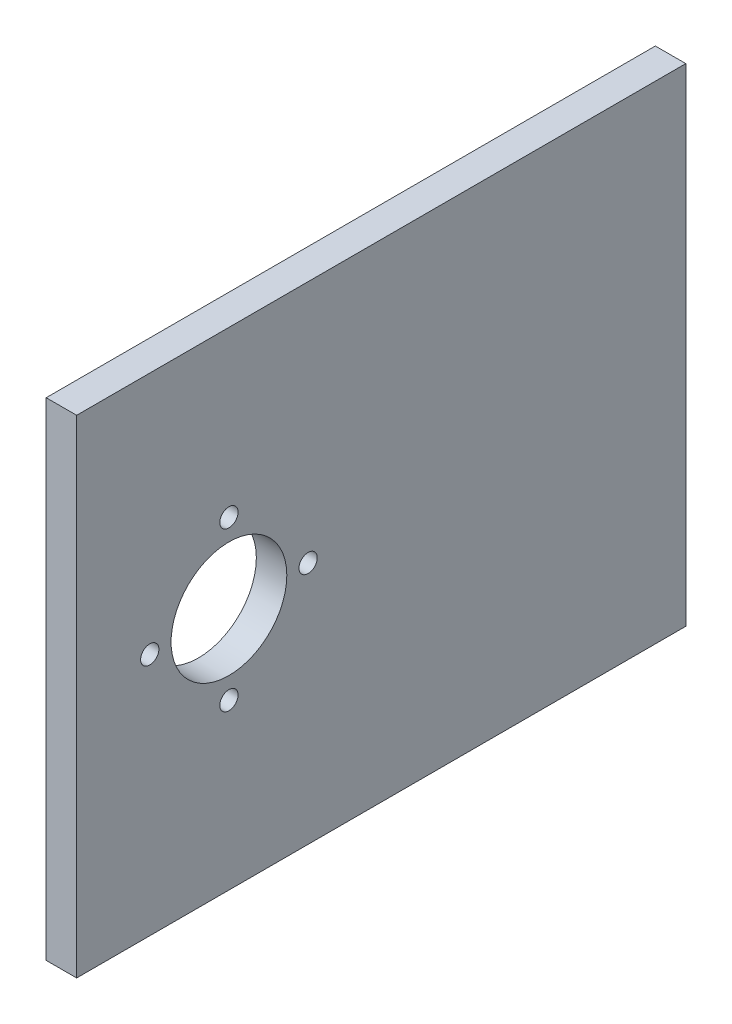
SolidWorks part; units mm, degrees
ref_plane "Front Plane" through (0, 0, 0) normal (1, 0, 0) x (0, 1, 0)
ref_plane "Top Plane" through (0, 0, 0) normal (0, 0, 1) x (0, 1, 0)
ref_plane "Right Plane" through (0, 0, 0) normal (0, 1, 0) x (-1, 0, 0)
sketch "Sketch1" plane through (0, 0, 0) normal (1, 0, 0) x (0, 1, 0)
  line L0 (-40, 25) -> (40, 25) construction
  line L1 (-40, -50) -> (40, -50)
  line L2 (-40, -50) -> (-40, 50)
  line L3 (-40, 50) -> (40, 50)
  line L4 (40, -50) -> (40, 50)
  line L5 (-40, -50) -> (40, 50) construction
  line L6 (-40, 50) -> (40, -50) construction
  line L7 (0, 50) -> (0, -50) construction
  circle A1 centre (0, 38) radius 1.5
  circle A2 centre (0, 12) radius 1.5
  circle A3 centre (-13, 25) radius 1.5
  circle A4 centre (13, 25) radius 1.5
  circle A5 centre (0, 25) radius 9.5
  point P0 (0, 0)
  dimension "D5" = 13
  dimension "D4" = 3
  dimension "D6" = 3
  dimension "D8" = 19
  dimension "D1" = 100
  dimension "D2" = 80
  dimension "D3" = 75
  dimension "D7" = 13
extrude "Boss-Extrude1" add sketch "Sketch1" along normal blind 5
